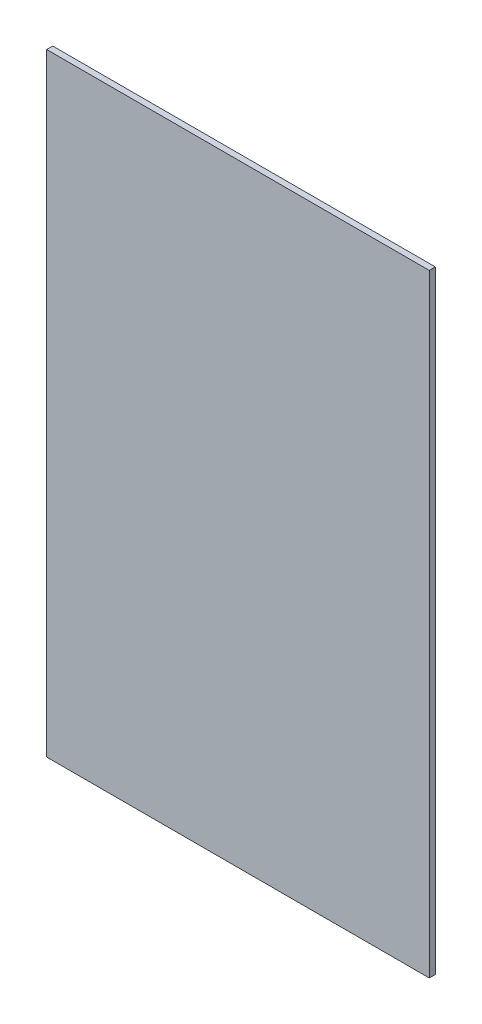
SolidWorks part; units mm, degrees
ref_plane "Спереди" through (0, 0, 0) normal (0, 0, 1) x (1, 0, 0)
ref_plane "Сверху" through (0, 0, 0) normal (0, 1, 0) x (1, 0, 0)
ref_plane "Справа" through (0, 0, 0) normal (1, 0, 0) x (0, 0, -1)
other "Configuration Table"
sketch "Эскиз1" plane through (0, 0, 0) normal (0, 0, 1) x (1, 0, 0)
  line L2 (-1162.3, -506.285) -> (-530, -506.285)
  line L3 (-1162.3, -506.285) -> (-1162.3, 506.285)
  line L4 (-1162.3, 506.285) -> (-530, 506.285)
  line L5 (-530, -506.285) -> (-530, 506.285)
extrude "Бобышка-Вытянуть1" add sketch "Эскиз1" against normal blind 10
equation "\"Глубина груза\"= 490"
equation "\"Высота груза\"= 297"
equation "\"Ширина ячейки\"= \"Ширина груза\" + 10"
equation "\"Глубина ячейки\"= \"Глубина груза\" + 10"
equation "\"Высота ячейки\"= \"Высота груза\" + 10 + 13"
equation "\"Колво ячеек ширина\"= 2"
equation "\"Колво ячеек высота\"= 2"
equation "\"Толщина стенки\"= 10"
equation "\"Крепление дверцы\"= 5"
equation "\"Ширина рейки\"= \"Толщина шестерни\""
equation "\"Высота рейки\"= 20"
equation "\"Высота пола\"= 20"
equation "\"Колво полозьев\"= 5"
equation "\"Отступ рейки\"= 20"
equation "\"Глубина каретки\"= \"Глубина ячейки\" + 30 + \"Мотор Y высота корпуса\" + 20"
equation "\"Длинна рейки\"= ( \"Ширина ячейки\" + \"Толщина стенки\" + \"Крепление дверцы\" ) * \"Колво ячеек ширина\" + \"Ширина ячейки выгрузки\" * \"Колво выгрузки\" + \"Толщина стенки\""
equation "\"Отступ шпильки\"= 26"
equation "\"Диаметр шпильки\"= 5"
equation "\"Длинна шпильки\"= ( \"Высота ячейки\" + \"Толщина стенки\" + \"Высота пола\" ) * \"Колво ячеек высота\" + ( \"Толщина стенки\" + \"Отступ рейки\" ) * 2 "
equation "\"Ширина пластины\"= 50  "
equation "\"Высота зона выгрузки\"= \"Высота ячейки\" * 2 + \"Толщина стенки\" * 2"
equation "\"Колво выгрузки\"= 1"
equation "\"Ширина ячейки выгрузки\"= \"Ширина ячейки\" + \"Толщина стенки\" + \"Отступ крепления мотора фиксации\"*2"
equation "\"Отступ крепления мотора фиксации\" = 30"
equation "\"Мотор X ширина корпуса\"= 42.3"
equation "\"Мотор X высота корпуса\"= 42.3"
equation "\"Мотор X длина корпуса\"= 40"
equation "\"Мотор X вылет вала\"= 19.8"
equation "\"Мотор Y ширина корпуса\"= 42.3"
equation "\"Мотор Y высота корпуса\"= 42.3"
equation "\"Мотор Y длина корпуса\"= 48"
equation "\"Мотор Y вылет вала\"= 30"
equation "\"Мотор Z ширина корпуса\"= 42"
equation "\"Мотор Z высота корпуса\"= 42"
equation "\"Мотор Z длина корпуса\"= 40"
equation "\"Мотор Z вылет вала\"= 23"
equation "\"Мотор диаметр вала ПРЕДВ\"= 5"
equation "\"Мотор шаг крепления ПРЕДВ\"= 31"
equation "\"Мотор диаметр отверстий ПРЕДВ\"= 3"
equation "\"Мотор глубина отверстий ПРЕДВ\"= 4.5"
equation "\"Мотор диаметр буртика ПРЕДВ\"= 22"
equation "\"Мотор высота буртика ПРЕДВ\"= 2"
equation "\"Мотор диаметр шкива ПРЕДВ\"= 16"
equation "\"Мотор длина шкива ПРЕДВ\"= 12"
equation "\"Мотор отступ шкива ПРЕДВ\"= 5"
equation "\"Мотор X шаг градусов\"= 1.8"
equation "\"Мотор Y шаг градусов\"= 1.8"
equation "\"Мотор Z шаг градусов\"= 1.8"
equation "\"Мотор Y диаметр ротора\"= 25.78"
equation "\"Толщина шестерни\"= 10"
equation "\"Ширина груза\"= 420"
equation "\"D1@Бобышка-Вытянуть1\"=\"Толщина стенки\""
